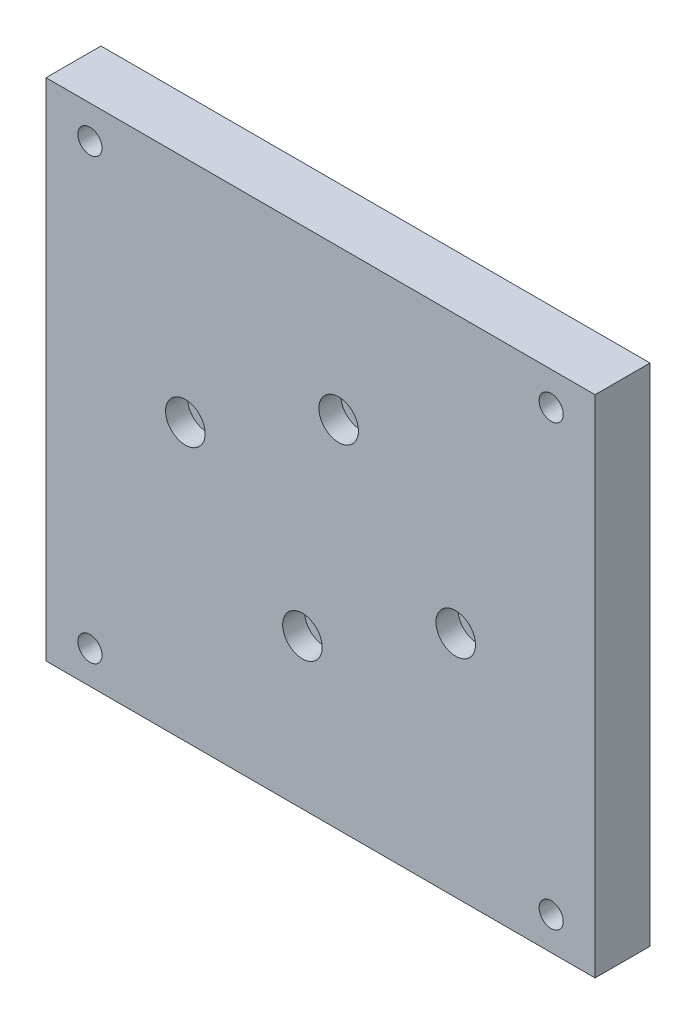
SolidWorks part; units mm, degrees
ref_plane "Front" through (0, 0, 0) normal (0, 0, 1) x (1, 0, 0)
ref_plane "Top" through (0, 0, 0) normal (0, 1, 0) x (1, 0, 0)
ref_plane "Right" through (0, 0, 0) normal (1, 0, 0) x (0, 0, -1)
sketch "草图1" plane through (0, 0, 0) normal (0, 0, 1) x (1, 0, 0)
  line L1 (25, -23) -> (-25, -23)
  line L2 (25, -23) -> (25, 23)
  line L3 (25, 23) -> (-25, 23)
  line L4 (-25, -23) -> (-25, 23)
  line L5 (25, -23) -> (-25, 23) construction
  line L6 (25, 23) -> (-25, -23) construction
  point P0 (0, 0)
  point P6 (-25, 0)
  dimension "D1" = 50
  dimension "D2" = 46
extrude "凸台-拉伸1" add sketch "草图1" along normal blind 5 contours L1 L4 L3 L2
sketch "草图2" plane through (0, 0, 5) normal (0, 0, 1) x (1, 0, 0)
  circle A0 centre (-1.6497, -9.3557) radius 1.025 construction
  circle A1 centre (12.3101, -2.1706) radius 1.025 construction
  circle A2 centre (1.6497, 9.3557) radius 1.025 construction
  circle A3 centre (-12.3101, 2.1706) radius 1.025 construction
  circle A4 centre (-1.6497, -9.3557) radius 1.025
  circle A5 centre (12.3101, -2.1706) radius 1.025
  circle A6 centre (1.6497, 9.3557) radius 1.025
  circle A7 centre (-12.3101, 2.1706) radius 1.025
extrude "切除-拉伸1" cut sketch "草图2" against normal blind 5
sketch "草图3" plane through (0, 0, 5) normal (0, 0, 1) x (1, 0, 0)
  circle A0 centre (-12.3101, 2.1706) radius 1.8
  circle A1 centre (1.6497, 9.3557) radius 1.8
  circle A2 centre (12.3101, -2.1706) radius 1.8
  circle A3 centre (-1.6497, -9.3557) radius 1.8
  dimension "D1" = 3.6
extrude "切除-拉伸2" cut sketch "草图3" against normal blind 2
sketch "草图4" plane through (0, 0, 0) normal (0, 0, -1) x (-1, 0, 0)
  line L0 (-25, -23) -> (25, -23) construction
  line L1 (25, -23) -> (25, 23) construction
  circle A0 centre (21, -20) radius 1.1
  circle A1 centre (-21, -20) radius 1.1
  dimension "D1" = 2.2
  dimension "D2" = 42
  dimension "D3" = 3
  dimension "D4" = 3
  dimension "D5" = 4
extrude "切除-拉伸3" cut sketch "草图4" against normal blind 24
ref_plane "基准面1" through (0, 0, 0) normal (0, -1, 0) x (-1, 0, 0)
mirror "镜向1" about plane through (0, 0, 0) normal (0, -1, 0) of "切除-拉伸3"
